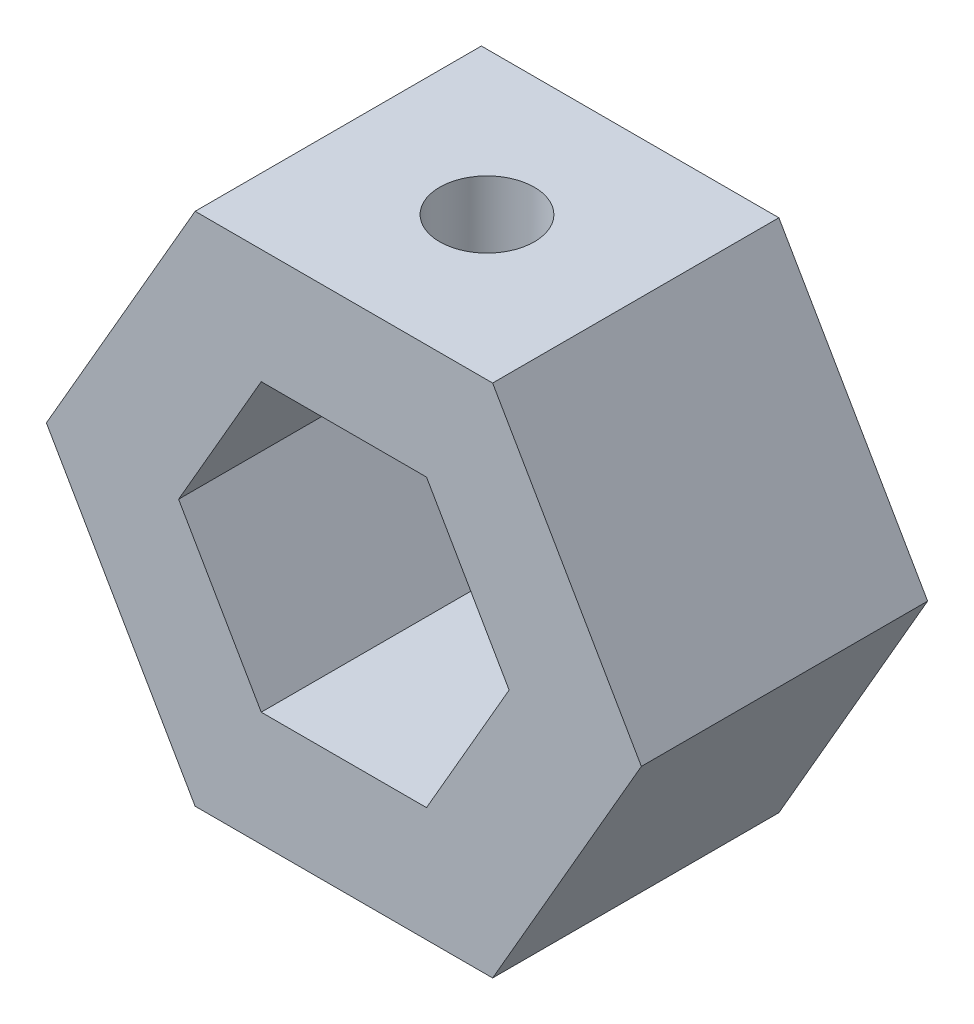
SolidWorks part; units mm, degrees
material "ABS"
ref_plane "Front Plane" through (0, 0, 0) normal (0, 0, 1) x (1, 0, 0)
ref_plane "Top Plane" through (0, 0, 0) normal (0, 1, 0) x (1, 0, 0)
ref_plane "Right Plane" through (0, 0, 0) normal (1, 0, 0) x (0, 0, -1)
sketch "Sketch1" plane through (0, 0, 0) normal (0, 0, 1) x (1, 0, 0)
  line L0 (6.5991, 11.43) -> (-6.5991, 11.43)
  line L1 (3.6662, -6.35) -> (7.3323, 0)
  line L2 (7.3323, 0) -> (3.6662, 6.35)
  line L3 (3.6662, 6.35) -> (-3.6662, 6.35)
  line L4 (-3.6662, 6.35) -> (-7.3323, 0)
  line L5 (-7.3323, 0) -> (-3.6662, -6.35)
  line L6 (-3.6662, -6.35) -> (3.6662, -6.35)
  line L7 (-6.5991, 11.43) -> (-13.1982, 0)
  line L8 (-13.1982, 0) -> (-6.5991, -11.43)
  line L9 (-6.5991, -11.43) -> (6.5991, -11.43)
  line L10 (6.5991, -11.43) -> (13.1982, 0)
  line L11 (13.1982, 0) -> (6.5991, 11.43)
  circle A0 centre (0, 0) radius 6.35 construction
  point P16 (0, 0)
  dimension "D1" = 12.7
  dimension "D2" = 5.08
extrude "Boss-Extrude1" add sketch "Sketch1" along normal blind 2.54 contours L5 L6 L1 L2 L3 L4 | L10 L11 L0 L7 L8 L9 L6 L5 L4 L3 L2 L1 region at (9.5963, 5.5404, 0) region at (0, 0, 0)
sketch "Sketch2" plane through (0, 0, 2.54) normal (0, 0, 1) x (1, 0, 0)
  point P0 (0, 0)
  point P1 (-17.2019, 6.9381)
hole_wizard "CSK for M3 Flat Head Machine Screw1" positions "Sketch2" profile "Sketch3" countersink size "M3" standard "ANSI Metric" end condition through all
sketch "Sketch3" plane through (0, 0, 2.54) normal (1, 0, 0) x (0, -1, 0)
  line L0 (0, 0) -> (0, 2.54)
  line L1 (0, 2.54) -> (1.7, 2.54)
  line L2 (1.7, 2.54) -> (1.7, 1.45)
  line L3 (1.7, 1.45) -> (3.15, 0)
  line L5 (3.15, 0) -> (0, 0)
  line L6 (-1.7, 1.45) -> (-3.15, 0) construction
  line L11 (0, -6.35) -> (0, 107.95) construction
  dimension "Thru Hole Dia." = 3.4
  dimension "Thru Hole Depth" = 2.54
  dimension "Near C'Sink Dia." = 6.3
  dimension "Near C'Sink Angle" = 90
extrude "Boss-Extrude2" add sketch "Sketch1<4>" along normal blind 12.7
sketch "Sketch1<4>" plane through (0, 0, 0) normal (0, 0, 1) x (1, 0, 0) same geometry as "Sketch1"
sketch "Sketch4" plane through (0, 11.43, 0) normal (0, 1, 0) x (1, 0, 0)
  line L0 (0, 0) -> (0, -12.7) construction
  line L1 (6.5991, 0) -> (-6.5991, 0) construction
  line L2 (6.5991, -12.7) -> (-6.5991, -12.7) construction
  point P6 (0, -6.35)
hole_wizard "M5x0.8 Tapped Hole1" positions "Sketch4" profile "Sketch5" tap size "M5x0.8" standard "ANSI Metric" end condition up to next
sketch "Sketch5" plane through (0, 11.43, 6.35) normal (1, 0, 0) x (0, 0, 1)
  line L0 (0, 0) -> (0, 5.08)
  line L1 (0, 5.08) -> (2.1, 5.08)
  line L2 (2.1, 5.08) -> (2.1, 0)
  line L5 (2.1, 0) -> (0, 0)
  line L11 (0, -6.35) -> (0, 107.95) construction
  dimension "Thru Tap Drill Dia." = 4.2
  dimension "Thru Tap Drill Depth" = 5.08
cosmetic thread "Hole Thread2" parameters "D2"=5
